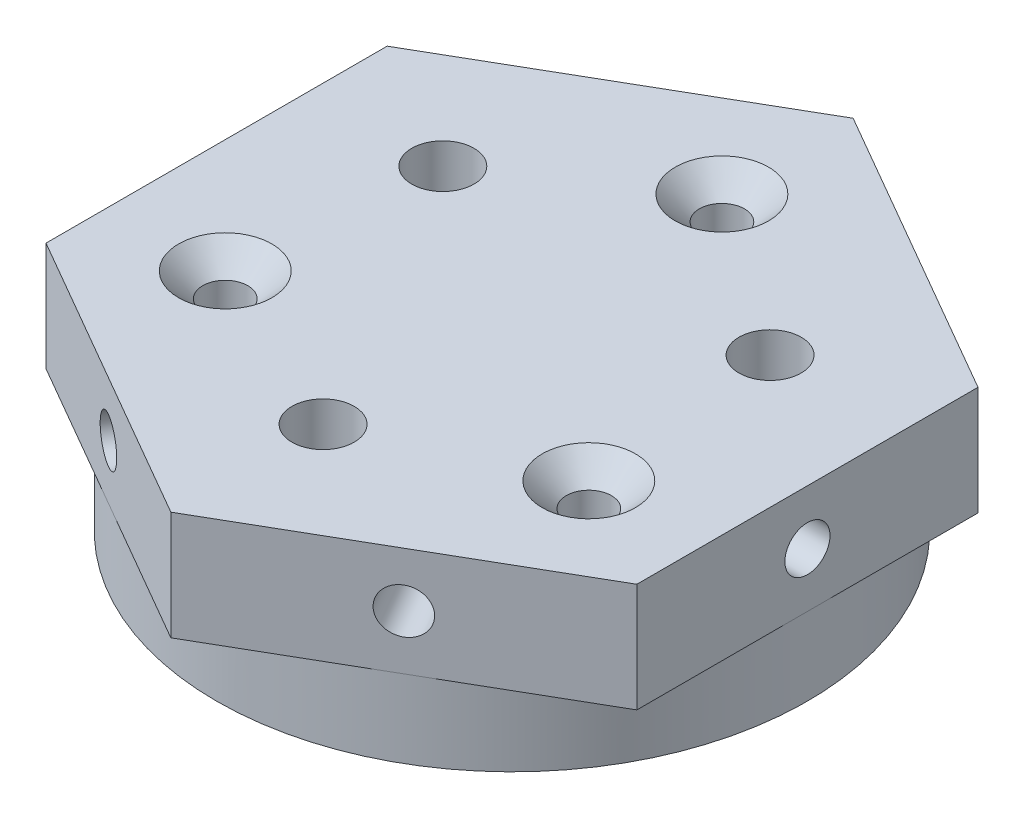
SolidWorks part; units mm, degrees
ref_plane "前视基准面" through (0, 0, 0) normal (0, 0, 1) x (1, 0, 0)
ref_plane "上视基准面" through (0, 0, 0) normal (0, 1, 0) x (1, 0, 0)
ref_plane "右视基准面" through (0, 0, 0) normal (1, 0, 0) x (0, 0, -1)
sketch "草图1" plane through (0, 0, 0) normal (0, 1, 0) x (1, 0, 0)
  line L0 (0, 0) -> (0, 33.3478) construction
  line L1 (0, 0) -> (11.2563, 0) construction
  point P0 (-27.5735, 20.7093)
  line B0 (-11.6913, -6.75) -> (0, 0) construction
  line B1 (0, 0) -> (11.6913, -6.75) construction
  line B2 (0, 0) -> (-10.5222, 6.075) construction
  line B3 (10.5222, 6.075) -> (0, 0) construction
  circle B4 centre (0, 0) radius 19
  circle B5 centre (0, 13.5) radius 1.45
  circle B6 centre (0, 0) radius 13.5 construction
  circle B7 centre (-11.6913, -6.75) radius 1.45
  circle B8 centre (11.6913, -6.75) radius 1.45
  circle B9 centre (0, 0) radius 12.15 construction
  circle B10 centre (-10.5222, 6.075) radius 2
  circle B11 centre (0, -12.15) radius 2
  circle B12 centre (10.5222, 6.075) radius 2
sketch_block_instance "块1-1"
sketch_block "块1" parameters "D1"=38, "D2"=27, "D3"=2.9, "D4"=24.3, "D5"=4
extrude "凸台-拉伸1" add sketch "草图1" along normal blind 12
sketch "草图2" plane through (0, 12, 0) normal (0, 1, 0) x (1, 0, 0)
  line L0 (0, 21.9393) -> (0, 0) construction
  line L1 (0, 21.9393) -> (-19, 10.9697)
  line L2 (-19, 10.9697) -> (-19, -10.9697)
  line L3 (-19, -10.9697) -> (0, -21.9393)
  line L4 (0, -21.9393) -> (19, -10.9697)
  line L5 (19, -10.9697) -> (19, 10.9697)
  line L6 (19, 10.9697) -> (0, 21.9393)
  circle A0 centre (0, 0) radius 19 construction
  circle A1 centre (0, 13.5) radius 1.45
  circle A2 centre (0, 13.5) radius 1.45 construction
  circle A3 centre (-10.5222, 6.075) radius 2
  circle A4 centre (-10.5222, 6.075) radius 2 construction
  circle A5 centre (10.5222, 6.075) radius 2
  circle A6 centre (10.5222, 6.075) radius 2 construction
  circle A7 centre (-11.6913, -6.75) radius 1.45
  circle A8 centre (-11.6913, -6.75) radius 1.45 construction
  circle A9 centre (0, -12.15) radius 2
  circle A10 centre (0, -12.15) radius 2 construction
  circle A11 centre (11.6913, -6.75) radius 1.45
  circle A12 centre (11.6913, -6.75) radius 1.45 construction
  dimension "D1" = 38
extrude "凸台-拉伸2" add sketch "草图2" against normal blind 7
sketch "草图3" plane through (9.5, 0, 16.4545) normal (0.5, 0, 0.866) x (0.866, 0, -0.5)
  line L1 (0, 12) -> (0, 5) construction
  line L2 (-10.9697, 12) -> (10.9697, 12) construction
  circle A1 centre (0, 8.5) radius 1.45
  dimension "D1" = 2.9
extrude "切除-拉伸1" cut sketch "草图3" against normal blind 8
sketch "草图4" plane through (-9.5, 0, 16.4545) normal (-0.5, 0, 0.866) x (0.866, 0, 0.5)
  line L0 (0, 5) -> (0, 12) construction
  line L1 (-10.9697, 12) -> (10.9697, 12) construction
  circle A0 centre (0, 8.5) radius 1.45
  dimension "D1" = 2.9
extrude "切除-拉伸2" cut sketch "草图4" against normal blind 8
sketch "草图5" plane through (-19, 0, 0) normal (-1, 0, 0) x (0, 0, 1)
  line L0 (0, 5) -> (0, 12) construction
  line L1 (-10.9697, 12) -> (10.9697, 12) construction
  circle A0 centre (0, 8.5) radius 1.45
  dimension "D1" = 2.9
extrude "切除-拉伸3" cut sketch "草图5" against normal blind 8
sketch "草图6" plane through (19, 0, 0) normal (1, 0, 0) x (0, 0, -1)
  line L0 (0, 12) -> (0, 5) construction
  line L1 (-10.9697, 12) -> (10.9697, 12) construction
  circle A0 centre (0, 8.5) radius 1.45
  dimension "D1" = 2.9
extrude "切除-拉伸4" cut sketch "草图6" against normal blind 8
sketch "草图7" plane through (9.5, 0, -16.4545) normal (0.5, 0, -0.866) x (-0.866, 0, -0.5)
  line L0 (0, 12) -> (0, 5) construction
  line L1 (-10.9697, 12) -> (10.9697, 12) construction
  circle A0 centre (0, 8.5) radius 1.45
  dimension "D1" = 2.9
extrude "切除-拉伸5" cut sketch "草图7" against normal blind 8
chamfer "倒角1" distance 1.55 angle 45 3 edges at (0, 12, -12.05) (-11.6913, 12, 8.2) (11.6913, 12, 8.2)
